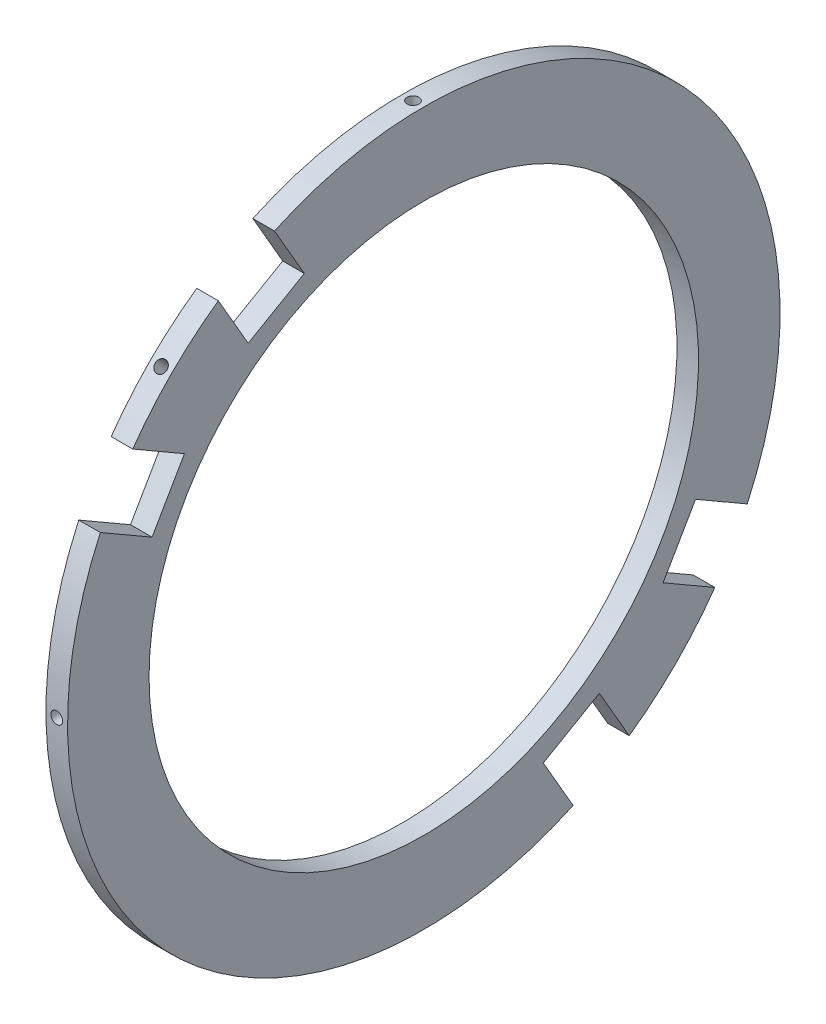
SolidWorks part; units mm, degrees
ref_plane "Front Plane" through (0, 0, 0) normal (0, 0, 1) x (1, 0, 0)
ref_plane "Top Plane" through (0, 0, 0) normal (0, 1, 0) x (1, 0, 0)
ref_plane "Right Plane" through (0, 0, 0) normal (1, 0, 0) x (0, 0, -1)
sketch "Ring Sketch" plane through (0, 0, 0) normal (0, 0, 1) x (1, 0, 0)
  line L0 (-1000, 0) -> (1000, 0) construction
  line L1 (-3, 76.35) -> (3, 76.35)
  line L2 (3, 76.35) -> (3, 99)
  line L3 (3, 99) -> (-3, 99)
  line L4 (-3, 99) -> (-3, 76.35)
revolve "Ring" add sketch "Ring Sketch" angle 360 about L0
ref_axis "Engine Axis" through (3.3, 0, 0) along (-1, 0, 0)
ref_plane "Notch Plane" through (3, 0, 0) normal (1, 0, 0) x (0, 0, -1)
sketch "Notch 30 Sketch" plane through (3, 0, 0) normal (1, 0, 0) x (0, 0, -1)
  line L0 (-48.7942, 66.5141) -> (-33.2058, 75.5141)
  line L1 (-33.2058, 75.5141) -> (-42.7058, 91.9686)
  line L2 (-42.7058, 91.9686) -> (-58.2942, 82.9686)
  line L3 (-58.2942, 82.9686) -> (-48.7942, 66.5141)
extrude "Notch 30" cut sketch "Notch 30 Sketch" against normal blind 6
sketch "Notch 60 Sketch" plane through (3, 0, 0) normal (1, 0, 0) x (0, 0, -1)
  line L0 (-75.5141, 33.2058) -> (-66.5141, 48.7942)
  line L1 (-66.5141, 48.7942) -> (-82.9686, 58.2942)
  line L2 (-82.9686, 58.2942) -> (-91.9686, 42.7058)
  line L3 (-91.9686, 42.7058) -> (-75.5141, 33.2058)
extrude "Notch 60" cut sketch "Notch 60 Sketch" against normal blind 6
sketch "Notch 210 Sketch" plane through (3, 0, 0) normal (1, 0, 0) x (0, 0, -1)
  line L0 (48.7942, -66.5141) -> (33.2058, -75.5141)
  line L1 (33.2058, -75.5141) -> (42.7058, -91.9686)
  line L2 (42.7058, -91.9686) -> (58.2942, -82.9686)
  line L3 (58.2942, -82.9686) -> (48.7942, -66.5141)
extrude "Notch 210" cut sketch "Notch 210 Sketch" against normal blind 6
sketch "Notch 240 Sketch" plane through (3, 0, 0) normal (1, 0, 0) x (0, 0, -1)
  line L0 (75.5141, -33.2058) -> (66.5141, -48.7942)
  line L1 (66.5141, -48.7942) -> (82.9686, -58.2942)
  line L2 (82.9686, -58.2942) -> (91.9686, -42.7058)
  line L3 (91.9686, -42.7058) -> (75.5141, -33.2058)
extrude "Notch 240" cut sketch "Notch 240 Sketch" against normal blind 6
sketch "Screw Hole Sketch" plane through (0, 0, 0) normal (0, 0, 1) x (1, 0, 0)
  line L0 (0, 30) -> (0, 150) construction
  line L1 (0, 91) -> (1.65, 91)
  line L2 (1.65, 91) -> (1.65, 100)
  line L3 (1.65, 100) -> (0, 100)
  line L4 (0, 100) -> (0, 91)
revolve "Screw Hole" cut sketch "Screw Hole Sketch" angle 360 about L0
pattern_circular "Screw Holes x8" count 8 over 360 about axis through (3.3, 0, 0) along (-1, 0, 0) of "Screw Hole"
